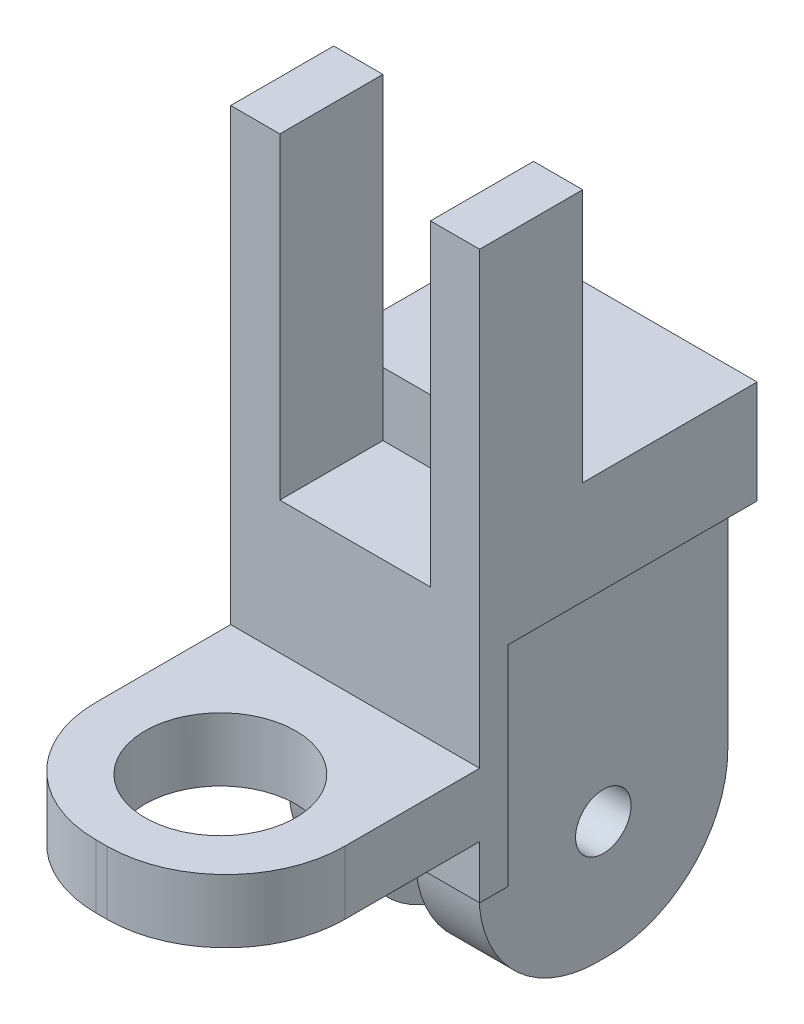
SolidWorks part; units mm, degrees
ref_plane "Front Plane" through (0, 0, 0) normal (0, 0, 1) x (1, 0, 0)
ref_plane "Top Plane" through (0, 0, 0) normal (0, 1, 0) x (1, 0, 0)
ref_plane "Right Plane" through (0, 0, 0) normal (1, 0, 0) x (0, 0, -1)
sketch "Sketch4" plane through (0, 0, 0) normal (0, 0, 1) x (1, 0, 0)
  line L0 (0, 82.063) -> (0, -112.4411) construction
  line L1 (-144.2959, 0) -> (145.5617, 0) construction
  line L2 (-12.7, 12.7) -> (-12.7, -12.7)
  line L3 (-15.7, 15.7) -> (15.7, 15.7)
  line L4 (-15.7, 15.7) -> (-15.7, -15.7)
  line L5 (-15.7, -15.7) -> (15.7, -15.7)
  line L6 (15.7, 15.7) -> (15.7, -15.7)
  line L7 (-12.7, -12.7) -> (12.7, -12.7)
  line L8 (12.7, 12.7) -> (12.7, -12.7)
  line L9 (-12.7, 12.7) -> (12.7, 12.7)
  dimension "D2" = 12.7
  dimension "D3" = 12.7
  dimension "D4" = 12.7
  dimension "D5" = 12.7
  dimension "D1" = 3
extrude "Boss-Extrude3" add sketch "Sketch4" along normal blind 30
sketch "Sketch5" plane through (0, 0, 30) normal (0, 0, 1) x (1, 0, 0)
  line L0 (-15.7, 15.7) -> (15.7, 15.7)
  line L1 (15.7, 15.7) -> (15.7, -15.7)
  line L2 (15.7, -15.7) -> (-15.7, -15.7)
  line L3 (-15.7, -15.7) -> (-15.7, 15.7)
extrude "Boss-Extrude4" add sketch "Sketch5" along normal blind 5
sketch "Sketch6" plane through (0, 0, 35) normal (0, 0, 1) x (1, 0, 0)
  line L0 (-14.6567, 0) -> (15.7, 0) construction
  line L1 (15.7, -15.7) -> (15.7, 15.7) construction
  line L2 (-15.7, 4) -> (15.7, 4)
  line L3 (-15.7, 15.7) -> (-15.7, -15.7) construction
  line L4 (15.7, 4) -> (15.7, -4)
  line L5 (15.7, -4) -> (-15.7, -4)
  line L6 (-15.7, -4) -> (-15.7, 4)
  dimension "D1" = 4
  dimension "D2" = 4
extrude "Boss-Extrude5" add sketch "Sketch6" along normal blind 5
sketch "Sketch7" plane through (0, -4, 0) normal (0, -1, 0) x (1, 0, 0)
  line L0 (-15.7, 40) -> (-15.7, 52)
  line L1 (-0.7, 67) -> (0.7, 67)
  line L2 (15.7, 52) -> (15.7, 40)
  line L3 (-15.7, 40) -> (15.7, 40) construction
  line L4 (15.7, 40) -> (-15.7, 40)
  line L5 (0, 0) -> (0, 92.3619) construction
  arc A0 (0.7, 67) -> (15.7, 52) centre (0.7, 52) cw
  arc A1 (-15.7, 52) -> (-0.7, 67) centre (-0.7, 52) cw
  point P9 (15.7, 67)
  point P12 (-15.7, 67)
  dimension "D3" = 15
  dimension "D1" = 27
  dimension "D2" = 31.4
extrude "Boss-Extrude6" add sketch "Sketch7" against normal blind 8
sketch "Sketch8" plane through (0, -4, 0) normal (0, -1, 0) x (1, 0, 0)
  line L0 (0, 67.4318) -> (0, -5.9603) construction
  line L1 (0.7, 67) -> (-0.7, 67) construction
  circle A0 centre (0, 52) radius 9.5
  dimension "D1" = 15
extrude "Boss-Extrude7" add sketch "Sketch8" along normal blind 8
mirror "Mirror1" about plane through (0, 0, 0) normal (0, 1, 0) of "Boss-Extrude7"
sketch "Sketch9" plane through (0, 15.7, 0) normal (0, 1, 0) x (1, 0, 0)
  line L1 (-15.7, -32) -> (15.7, -32)
  line L2 (-15.7, -35) -> (-15.7, 0) construction
  line L3 (15.7, -35) -> (15.7, 0) construction
  line L4 (0, 15.8647) -> (0, -78.6922) construction
  line L5 (0, -52) -> (31.7707, -52) construction
  line L6 (31.7707, -52) -> (-30.9902, -52) construction
  line L7 (-15.7, -32) -> (-15.7, -22)
  line L8 (-15.7, -22) -> (15.7, -22)
  line L9 (15.7, -22) -> (15.7, -32)
  dimension "D1" = 20
  dimension "D2" = 10
extrude "Boss-Extrude8" add sketch "Sketch9" along normal blind 5
sketch "Sketch10" plane through (0, 15.7, 0) normal (0, 1, 0) x (1, 0, 0)
  line L0 (-15.7, -22) -> (-15.7, -12)
  line L1 (-15.7, -22) -> (-15.7, 0) construction
  line L2 (-15.7, -12) -> (15.7, -12)
  line L3 (15.7, -22) -> (15.7, 0) construction
  line L4 (15.7, -12) -> (15.7, -22)
  line L5 (15.7, -22) -> (-15.7, -22)
  dimension "D1" = 10
extrude "Boss-Extrude9" add sketch "Sketch10" along normal blind 13
sketch "Sketch11" plane through (0, 20.7, 0) normal (0, 1, 0) x (1, 0, 0)
  line L0 (-15.7, -22) -> (-9.5, -22)
  line L1 (15.7, -22) -> (-15.7, -22) construction
  line L2 (-9.5, -22) -> (-9.5, -32)
  line L3 (-15.7, -32) -> (15.7, -32) construction
  line L4 (-9.5, -32) -> (-15.7, -32)
  line L5 (-15.7, -32) -> (-15.7, -22)
  line L6 (9.5, -22) -> (9.5, -32)
  line L7 (-15.7, -22) -> (15.7, -22) construction
  line L8 (-15.7, -32) -> (15.7, -32) construction
  line L9 (9.5, -32) -> (15.7, -32)
  line L10 (15.7, -32) -> (15.7, -22)
  line L11 (15.7, -32) -> (15.7, -22) construction
  line L12 (15.7, -22) -> (9.5, -22)
  dimension "D1" = 6.2
  dimension "D2" = 6.2
extrude "Boss-Extrude10" add sketch "Sketch11" along normal blind 40
sketch "Sketch12" plane through (0, 0, 32) normal (0, 0, 1) x (1, 0, 0)
  line L0 (-15.7, 60.7) -> (-9.5, 60.7)
  line L1 (-9.5, 60.7) -> (-9.5, 20.7)
  line L2 (-9.5, 20.7) -> (9.5, 20.7)
  line L3 (9.5, 20.7) -> (9.5, 60.7)
  line L4 (9.5, 60.7) -> (15.7, 60.7)
  line L5 (15.7, 60.7) -> (15.7, 15.7)
  line L6 (15.7, 15.7) -> (-15.7, 15.7)
  line L7 (-15.7, 15.7) -> (-15.7, 60.7)
extrude "Boss-Extrude11" add sketch "Sketch12" along normal blind 3
sketch "Sketch13" plane through (-15.7, 0, 0) normal (-1, 0, 0) x (0, 0, 1)
  line L5 (0, 15.7) -> (31.4, 15.7)
  line L6 (31.4, 15.7) -> (31.4, -15.7)
  line L7 (35, -15.7) -> (0, -15.7) construction
  line L8 (31.4, -15.7) -> (0, -15.7)
  line L9 (0, -15.7) -> (0, 15.7)
  dimension "D1" = 31.4
extrude "Cut-Extrude1" cut sketch "Sketch13" against normal blind 31.4
sketch "Sketch15" plane through (0, 0, 12) normal (0, 0, -1) x (-1, 0, 0)
  line L0 (-15.7, 28.7) -> (15.7, 28.7)
  line L1 (15.7, 28.7) -> (15.7, 15.7)
  line L2 (15.7, 15.7) -> (-15.7, 15.7)
  line L3 (-15.7, 15.7) -> (-15.7, 28.7)
extrude "Boss-Extrude12" add sketch "Sketch15" along normal blind 12
sketch "Sketch17" plane through (0, 15.7, 0) normal (0, -1, 0) x (1, 0, 0)
  line L0 (0, 70.9174) -> (0, -6.6676) construction
  line L1 (-12, 31.4) -> (-12, 0)
  line L2 (15.7, 31.4) -> (-15.7, 31.4) construction
  line L3 (15.7, 0) -> (-15.7, 0) construction
  line L4 (-12, 0) -> (-4, 0)
  line L5 (-4, 0) -> (-4, 31.4)
  line L6 (15.7, 31.4) -> (-15.7, 31.4) construction
  line L7 (-4, 31.4) -> (-12, 31.4)
  line L8 (-15.7, 31.4) -> (-15.7, 0) construction
  dimension "D1" = 8
  dimension "D2" = 3.7
  dimension "D3" = 4
extrude "Boss-Extrude13" add sketch "Sketch17" along normal blind 10
sketch "Sketch18" plane through (-12, 0, 0) normal (-1, 0, 0) x (0, 0, 1)
  line L1 (31.4, 5.7) -> (0, 5.7)
  line L4 (0, 5.7) -> (0, -13.3)
  line L5 (15, -28.3) -> (16.4, -28.3)
  line L6 (31.4, -13.3) -> (31.4, 5.7)
  arc A3 (16.4, -28.3) -> (31.4, -13.3) centre (16.4, -13.3) ccw
  arc A4 (0, -13.3) -> (15, -28.3) centre (15, -13.3) ccw
  circle A5 centre (15.7, -13.3) radius 3.5
  point P12 (0, -28.3)
  dimension "D1" = 34
  dimension "D2" = 15
  dimension "D3" = 15
  dimension "D4" = 15.7
extrude "Boss-Extrude14" add sketch "Sketch18" against normal blind 8
mirror "Mirror3" about plane through (0, 0, 0) normal (1, 0, 0) of "Boss-Extrude13", "Boss-Extrude14"
sketch "Sketch19" plane through (15.7, 0, 0) normal (1, 0, 0) x (0, 0, -1)
  line L0 (-31.4, -10.7) -> (-35, -10.7)
  line L3 (-31.4, -15.7) -> (-31.4, 15.7) construction
  line L4 (-35, -15.7) -> (-35, -4) construction
  line L5 (-35, -10.7) -> (-35, -15.7)
  line L6 (-35, -15.7) -> (-31.4, -15.7)
  line L7 (-31.4, -15.7) -> (-31.4, -10.7)
  dimension "D1" = 5
extrude "Cut-Extrude2" cut sketch "Sketch19" against normal blind 31.4
extrude "Cut-Extrude3" cut sketch "Sketch8<2>" against normal blind 24 from offset 8
sketch "Sketch8<2>" plane through (0, -4, 0) normal (0, -1, 0) x (1, 0, 0) same geometry as "Sketch8"
sketch "Sketch20" plane through (0, -10.7, 0) normal (0, -1, 0) x (1, 0, 0)
  line L0 (-4, 31.4) -> (-4, 32.4)
  line L1 (-4, 32.4) -> (4, 32.4)
  line L2 (4, 32.4) -> (4, 31.4)
  line L3 (4, 31.4) -> (-4, 31.4)
  dimension "D1" = 1
extrude "Cut-Extrude4" cut sketch "Sketch20" against normal blind 26.4
